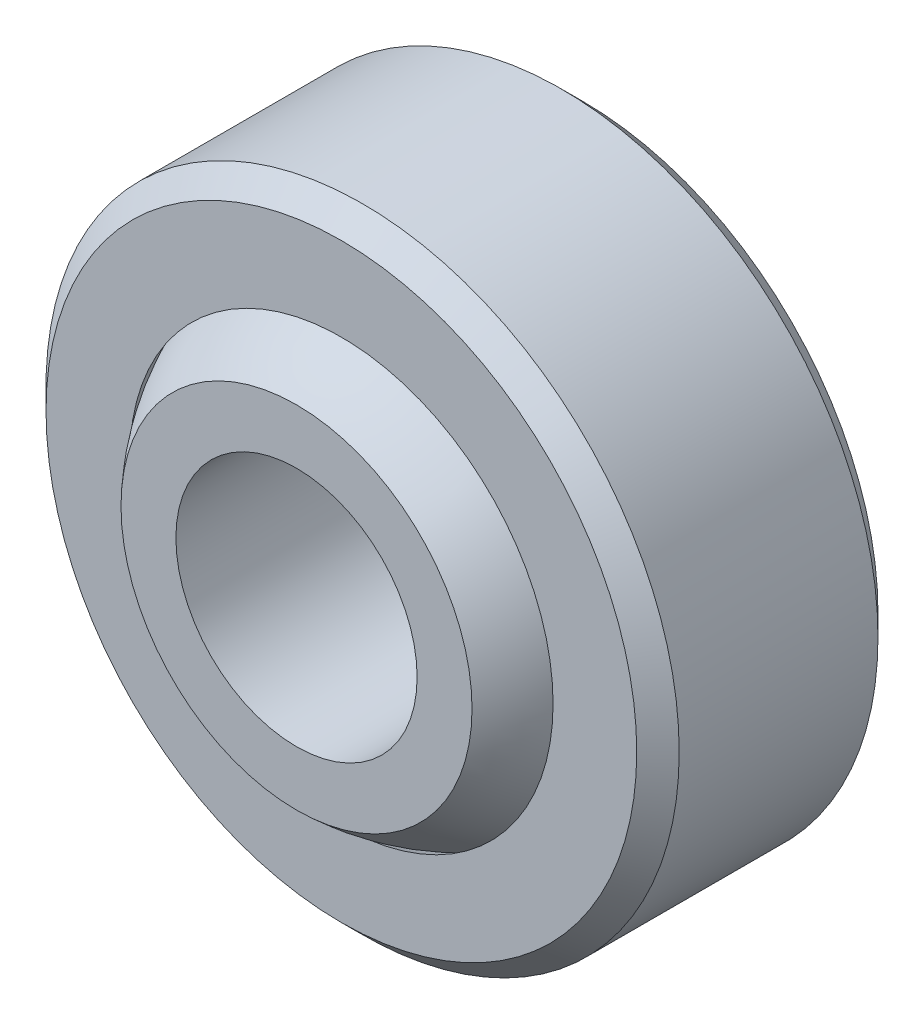
SolidWorks part; units mm, degrees
ref_plane "Front" through (0, 0, 0) normal (0, 0, 1) x (1, 0, 0)
ref_plane "Top" through (0, 0, 0) normal (0, 1, 0) x (1, 0, 0)
ref_plane "Right" through (0, 0, 0) normal (1, 0, 0) x (0, 0, -1)
sketch "Sketch1" plane through (0, 0, 0) normal (0, 0, 1) x (1, 0, 0)
  circle A0 centre (0, 0) radius 3.175 construction
  circle A1 centre (0, 0) radius 6.35 construction
  circle A2 centre (0, 0) radius 6.4135 construction
  circle A3 centre (0, 0) radius 8.3337
  dimension "D OD" = 16.6675
  dimension "B Hole Dia" = 6.35
  dimension "Ball Dia" = 12.7
  dimension "D1" = 12.827
extrude "Extrude1" add sketch "Sketch1" along normal mid plane 6.35
sketch "Sketch2" plane through (0, 0, 0) normal (0, 0, 1) x (1, 0, 0)
  line L0 (0, 6.4135) -> (0, -6.4135)
  line L1 (0, 6.4135) -> (0, 8.3337) construction
  circle A0 centre (0, 0) radius 6.4135 construction
  arc A1 (0, -6.4135) -> (0, 6.4135) centre (0, 0) ccw
  circle A2 centre (0, 0) radius 8.3337 construction
revolve "Cut-Revolve1" cut sketch "Sketch2" angle 360 about L1
sketch "Sketch3" plane through (0, 0, 0) normal (0, 0, 1) x (1, 0, 0)
  line L0 (0, 6.35) -> (0, -6.35)
  line L1 (0, 6.35) -> (0, 8.3337) construction
  circle A0 centre (0, 0) radius 6.35 construction
  arc A1 (0, -6.35) -> (0, 6.35) centre (0, 0) ccw
  circle A2 centre (0, 0) radius 8.3337 construction
revolve "Revolve1" add sketch "Sketch3" angle 360 about L1
sketch "Sketch4" plane through (0, 0, 0) normal (0, 0, 1) x (1, 0, 0)
  circle A0 centre (0, 0) radius 3.175 construction
  circle A1 centre (0, 0) radius 3.175
extrude "Cut-Extrude1" cut sketch "Sketch4" against normal through all and the other way through all
sketch "Sketch5" plane through (0, 0, 0) normal (1, 0, 0) x (0, 0, -1)
  line L0 (-4.3561, 8.3337) -> (4.3561, 8.3337) construction
  line L1 (-4.3561, 8.3337) -> (-5.4993, 8.3337)
  line L2 (-4.3561, 8.3337) -> (-4.3561, -8.3337)
  line L3 (-4.3561, -8.3337) -> (-5.4993, -8.3337)
  line L4 (-5.4993, 8.3337) -> (-5.4993, -8.3337)
  line L5 (4.3561, -8.3337) -> (5.4993, -8.3337)
  line L6 (4.3561, -8.3337) -> (4.3561, 8.3337)
  line L7 (4.3561, 8.3337) -> (5.4993, 8.3337)
  line L8 (5.4993, -8.3337) -> (5.4993, 8.3337)
  line L16 (3.175, 8.3337) -> (-3.175, 8.3337) construction
  line L17 (5.4993, -3.175) -> (5.4993, 3.175) construction
  line L18 (-5.4993, -3.175) -> (-5.4993, 3.175) construction
  line L19 (-4.3561, -8.3337) -> (4.3561, -8.3337) construction
  line L20 (-3.175, -8.3337) -> (3.175, -8.3337) construction
  line L21 (0, 0) -> (-4.3561, 1.0458) construction
  line L22 (0, 0) -> (-4.3561, -1.0458) construction
  dimension "W ball Width" = 8.7122
  dimension "Mis Angle" = 27
extrude "Cut-Extrude2" cut sketch "Sketch5" against normal through all and the other way through all
chamfer "Chamfer1" distance 0.5588 angle 45 2 edges at (8.3337, 0, 3.175) (8.3337, 0, -3.175)
sketch "Sketch7" plane through (0, 0, 0) normal (1, 0, 0) x (0, 0, -1)
  line L0 (0, 0) -> (-4.3561, -1.0458) construction
  line L1 (0, 0) -> (-4.3561, 1.0458) construction
  line L2 (0, 0) -> (-4.3561, -1.0458) construction
  line L3 (0, 0) -> (-4.3561, 1.0458) construction
  line L4 (4.3561, 3.175) -> (-4.3561, 3.175)
  line L5 (-4.3561, -3.175) -> (4.3561, -3.175)
  line L6 (-4.3561, -3.175) -> (4.3561, -3.175) construction
  line L7 (4.3561, 3.175) -> (-4.3561, 3.175) construction
  arc A0 (3.175, 5.5725) -> (-3.175, 5.5725) centre (0, 0) ccw
  arc A1 (-3.175, -5.5725) -> (3.175, -5.5725) centre (0, 0) ccw
  arc A2 (-3.175, -5.5725) -> (3.175, -5.5725) centre (0, 0) ccw construction
  arc A3 (3.175, 5.5725) -> (-3.175, 5.5725) centre (0, 0) ccw construction
ref_axis "Center Axis 1" through (0, 0, -3.9256) along (0, 0, 1)
ref_plane "Contact Plane 1" through (0, 0, 4.3561) normal (0, 0, 1) x (1, 0, 0)
ref_plane "Contact Plane 2" through (0, 0, -4.3561) normal (0, 0, -1) x (-1, 0, 0)
equation "\"D1@Sketch1\"=\"Ball Dia@Sketch1\"*1.01"
